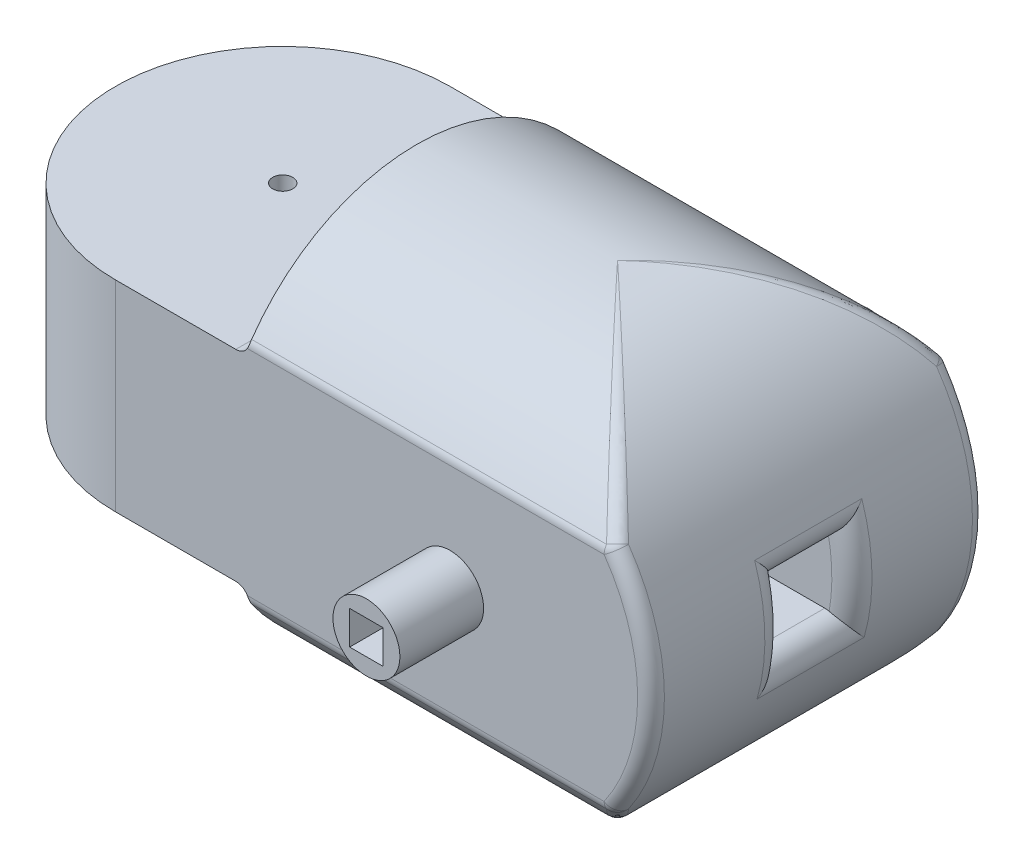
SolidWorks part; units mm, degrees
ref_plane "Front Plane" through (0, 0, 0) normal (0, 0, 1) x (1, 0, 0)
ref_plane "Top Plane" through (0, 0, 0) normal (0, 1, 0) x (1, 0, 0)
ref_plane "Right Plane" through (0, 0, 0) normal (1, 0, 0) x (0, 0, -1)
sketch "Sketch1" plane through (0, 0, 0) normal (1, 0, 0) x (0, 0, -1)
  line L0 (0, 60) -> (0, -60) construction
  line L1 (-50, 33.1662) -> (-50, -33.1662)
  line L2 (50, 33.1662) -> (50, -33.1662)
  circle A0 centre (0, 0) radius 60
  dimension "D1" = 120
  dimension "D2" = 50
  dimension "D3" = 50
extrude "Boss-Extrude1" add sketch "Sketch1" against normal blind 60 contours L0 A0 L1 | A0 L0 L2 region at (0, 0, -22.9942) region at (0, 0, 22.9942)
sketch "Sketch2" plane through (-60, 0, 0) normal (-1, 0, 0) x (0, 0, 1)
  line L0 (-50, -33.1662) -> (-50, 33.1662) construction
  line L1 (50, 30) -> (-50, 30)
  line L2 (50, 30) -> (50, -30)
  line L3 (50, -30) -> (-50, -30)
  line L4 (-50, 30) -> (-50, -30)
  line L5 (50, 30) -> (-50, -30) construction
  line L6 (50, -30) -> (-50, 30) construction
  point P0 (0, 0)
  dimension "D1" = 60
extrude "Boss-Extrude2" add sketch "Sketch2" along normal blind 90
sketch "Sketch3" plane through (0, 30, 0) normal (0, 1, 0) x (1, 0, 0)
  line L0 (-150, 50) -> (-60, 50) construction
  line L1 (-150, -50) -> (-60, -50) construction
  line L2 (-150, -50) -> (-150, 50) construction
  line L3 (-100, 50) -> (-150, 50)
  line L4 (-150, 50) -> (-150, -50)
  line L5 (-150, -50) -> (-100, -50)
  arc A0 (-100, 50) -> (-100, -50) centre (-100, 0) ccw
  line M2 (-60, 50) -> (-150, 50)
  line M3 (-150, 50) -> (-150, -50)
  line M4 (-150, -50) -> (-60, -50)
  dimension "D1" = 50
extrude "Cut-Extrude1" cut sketch "Sketch3" against normal through all contours A0 L4 M4 | A0 M2 M3 region at (-138.8316, 30, -38.8316) region at (-138.8316, 30, 38.8316)
sketch "Sketch4" plane through (0, 30, 0) normal (0, 1, 0) x (1, 0, 0)
  line L0 (-150, 0) -> (-100, 0) construction
  arc A0 (-100, 50) -> (-100, -50) centre (-100, 0) ccw construction
  circle A1 centre (-100, 0) radius 3
  dimension "D2" = 6
  dimension "D1" = 50
extrude "Cut-Extrude2" cut sketch "Sketch4" against normal through all
sketch "Sketch6" plane through (0, -30, 0) normal (0, -1, 0) x (-1, 0, 0)
  line L0 (131, -10.5) -> (91, -10.5)
  line L1 (91, -10.5) -> (91, 10.5)
  line L2 (91, 10.5) -> (131, 10.5)
  line L3 (131, 10.5) -> (131, -10.5)
  line L5 (131, 0) -> (91, 0) construction
  line L6 (150, 0) -> (60, 0) construction
  line L7 (60, 50) -> (60, -50) construction
  line L8 (100, 50) -> (100, -50) construction
  arc A0 (100, -50) -> (100, 50) centre (100, 0) ccw construction
  dimension "D1" = 9
  dimension "D2" = 40
  dimension "D3" = 21
extrude "Cut-Extrude3" cut sketch "Sketch6" against normal blind 30
sketch "Sketch7" plane through (0, 0, 0) normal (0, 0, 1) x (1, 0, 0)
  circle A0 centre (0, 0) radius 10
  dimension "D2" = 20
extrude "Boss-Extrude3" add sketch "Sketch7" along normal mid plane 150
sketch "Sketch8" plane through (0, 0, 75) normal (0, 0, 1) x (1, 0, 0)
  line L1 (-5, 5) -> (5, 5)
  line L2 (-5, 5) -> (-5, -5)
  line L3 (-5, -5) -> (5, -5)
  line L4 (5, 5) -> (5, -5)
  line L5 (-5, 5) -> (5, -5) construction
  line L6 (-5, -5) -> (5, 5) construction
  point P0 (0, 0)
  dimension "D1" = 10
extrude "Cut-Extrude4" cut sketch "Sketch8" against normal blind 10
sketch "Sketch9" plane through (0, 0, 0) normal (0, 0, 1) x (1, 0, 0)
  line L0 (0, 60) -> (0, -60)
  arc A0 (0, -60) -> (0, 60) centre (0, 0) ccw
extrude "Boss-Extrude4" add sketch "Sketch9" along normal mid plane 100
sketch "Sketch10" plane through (0, 0, 0) normal (1, 0, 0) x (0, 0, -1)
  line L0 (0, 60) -> (0, -60) construction
  line L1 (-50, 33.1662) -> (-50, -33.1662)
  line L2 (50, 33.1662) -> (50, -33.1662)
  line L3 (50, -60) -> (50, 60) construction
  line L4 (-50, 60) -> (50, 60)
  line L5 (-50, 60) -> (-50, -60)
  line L6 (-50, -60) -> (50, -60)
  line L7 (50, 60) -> (50, -60)
  line L8 (-50, 60) -> (50, -60) construction
  line L9 (-50, -60) -> (50, 60) construction
  circle A0 centre (0, 0) radius 60
  dimension "D1" = 120
  dimension "D2" = 50
  dimension "D3" = 50
extrude "Cut-Extrude7" cut sketch "Sketch10" along normal through all contours A0 L5 L6 | A0 L6 L7 | A0 L7 L4 | A0 L4 L5 region at (0, 52.3919, 38.1269) region at (0, -52.3919, 38.1269) region at (0, 52.3919, -38.1269) region at (0, -52.3919, -38.1269)
sketch "Sketch11" plane through (-91, 0, 0) normal (-1, 0, 0) x (0, 0, 1)
  line L0 (-14.0516, -9) -> (8.9809, -9) construction
  line L1 (0, 0) -> (0, -3) construction
  line L2 (-10.5, 0) -> (10.5, 0) construction
  line L3 (-5, -9) -> (5, -9)
  line L4 (-5, -9) -> (-5, -3)
  line L5 (-5, -3) -> (5, -3)
  line L6 (5, -3) -> (5, -9)
  dimension "D1" = 9
  dimension "D2" = 6
  dimension "D3" = 10
extrude "Cut-Extrude8" cut sketch "Sketch11" against normal through all
sketch "Sketch12" plane through (0, 0, -75) normal (0, 0, -1) x (-1, 0, 0)
  line L1 (-5, 3) -> (5, 3)
  line L2 (-5, 3) -> (-5, -3)
  line L3 (-5, -3) -> (5, -3)
  line L4 (5, 3) -> (5, -3)
  line L5 (-5, 3) -> (5, -3) construction
  line L6 (-5, -3) -> (5, 3) construction
  point P0 (0, 0)
  dimension "D1" = 10
  dimension "D2" = 6
extrude "Cut-Extrude9" cut sketch "Sketch12" against normal blind 75
fillet "Fillet1" radius 4 12 edges at (-5, -33.1662, -50) (-60, -30, 0) (-5, -33.1662, 50) (-5, 33.1662, 50) (-5, 33.1662, -50) (-60, 30, 0) (60, 0, 50) (28.3727, 52.8676, 28.3727) (28.3727, 52.8676, -28.3727) (60, 0, -50) (28.3727, -52.8676, -28.3727) (28.3727, -52.8676, 28.3727)
ref_plane "Plane1" through (60, 0, 0) normal (1, 0, 0) x (0, 0, -1)
sketch "Sketch13" plane through (60, 0, 0) normal (1, 0, 0) x (0, 0, -1)
  line L0 (-10, -9) -> (10, -9)
  line L1 (10, -9) -> (10, 11)
  line L2 (10, 11) -> (-10, 11)
  line L3 (-10, 11) -> (-10, -9)
  line L4 (0, 11) -> (0, 60) construction
  dimension "D1" = 20
  dimension "D2" = 20
extrude "Cut-Extrude10" cut sketch "Sketch13" against normal blind 65
fillet "Fillet2" radius 6 4 edges at (59.9914, 1.0142, -10) (58.983, 11, 0) (59.9914, 1.0142, 10) (59.3212, -9, 0)
